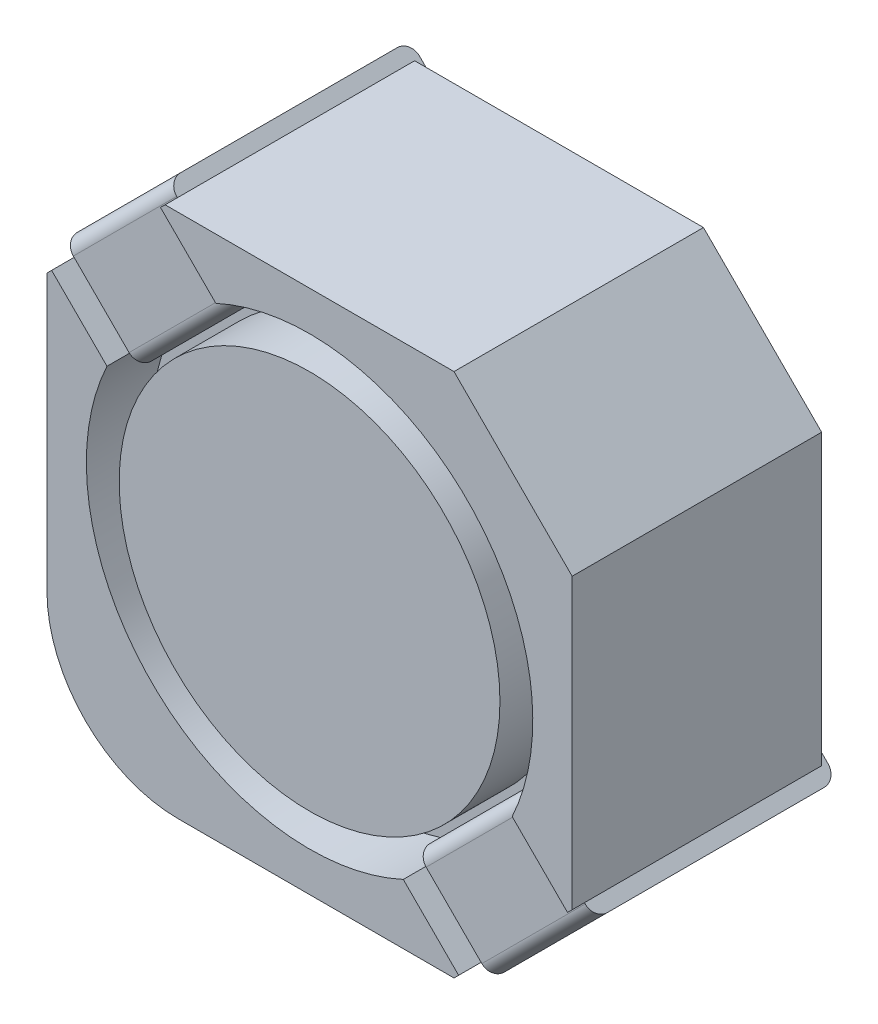
SolidWorks part; units mm, degrees
ref_plane "Спереди" through (0, 0, 0) normal (0, 0, 1) x (1, 0, 0)
ref_plane "Сверху" through (0, 0, 0) normal (0, 1, 0) x (1, 0, 0)
ref_plane "Справа" through (0, 0, 0) normal (1, 0, 0) x (0, 0, -1)
sketch "Эскиз2" plane through (0, 0, 0) normal (0, 0, 1) x (1, 0, 0)
  line L1 (-1.1, 2) -> (1.1, 2)
  line L2 (-2, 1.1) -> (-2, -1)
  line L3 (-1, -2) -> (1.1, -2)
  line L4 (2, 1.1) -> (2, -1.1)
  line L6 (-2, 1.1) -> (-1.1, 2)
  line L8 (1.1, 2) -> (2, 1.1)
  line L9 (1.1, -2) -> (2, -1.1)
  arc A0 (-2, -1) -> (-1, -2) centre (-1, -1) ccw
  point P0 (-2, 2)
  point P1 (2, -2)
  point P3 (2, 2)
  dimension "D1" = 1
extrude "Вытянуть1" add sketch "Эскиз2" along normal blind 1.9 from offset 0.1
sketch "Эскиз6" plane through (0, 0, 0) normal (0, 0, 1) x (1, 0, 0)
  circle A1 centre (0, 0) radius 1.7
extrude "Вытянуть5" cut sketch "Эскиз6" along normal blind 0.3
sketch "Эскиз8" plane through (0, 0, 0) normal (0, 0, 1) x (1, 0, 0)
  circle A0 centre (0, 0) radius 1.45
extrude "Вытянуть9" add sketch "Эскиз8" along normal blind 0.25 from offset 0.1
ref_plane "Плоскость1" through (-0.45, -0.45, 0) normal (0.7071, 0.7071, 0) x (0, 0, -1)
sketch "Эскиз10" plane through (-0.45, -0.45, 0) normal (0.7071, 0.7071, 0) x (0, 0, -1)
  line L0 (0, 1.6) -> (0, 2.2)
  line L1 (-0.1, 2.3) -> (-1.75, 2.3)
  line L2 (-1.85, 2.2) -> (-1.85, 1.6)
  line L3 (0, 0) -> (-3.3921, 0) construction
  line L4 (-1.75, -1.5) -> (-0.1, -1.5)
  line L5 (-1.75, 1.5) -> (-0.1, 1.5)
  line L6 (-1.85, -2.2) -> (-1.85, -1.6)
  line L7 (-0.1, -2.3) -> (-1.75, -2.3)
  line L8 (0, -1.6) -> (0, -2.2)
  arc A0 (0, 2.2) -> (-0.1, 2.3) centre (-0.1, 2.2) ccw
  arc A1 (0, 1.6) -> (-0.1, 1.5) centre (-0.1, 1.6) cw
  arc A2 (-1.85, 1.6) -> (-1.75, 1.5) centre (-1.75, 1.6) ccw
  arc A3 (-1.75, 2.3) -> (-1.85, 2.2) centre (-1.75, 2.2) ccw
  arc A4 (-1.75, -2.3) -> (-1.85, -2.2) centre (-1.75, -2.2) cw
  arc A5 (-1.85, -1.6) -> (-1.75, -1.5) centre (-1.75, -1.6) cw
  arc A6 (0, -1.6) -> (-0.1, -1.5) centre (-0.1, -1.6) ccw
  arc A7 (0, -2.2) -> (-0.1, -2.3) centre (-0.1, -2.2) cw
ref_plane "Плоскость2" through (0.45, 0.45, 0) normal (-0.7071, -0.7071, 0) x (0.7071, -0.7071, 0)
extrude "Вытянуть12" cut sketch "Эскиз6<3>" against normal blind 0.6 from offset 2.1
sketch "Эскиз6<3>" plane through (0, 0, 0) normal (0, 0, 1) x (1, 0, 0) same geometry as "Эскиз6"
sketch "Эскиз12" plane through (-0.45, -0.45, 0) normal (0.7071, 0.7071, 0) x (0, 0, -1)
  line L0 (-3.9996, 0) -> (-2.5383, 0) construction
  line L1 (-3.05, 2.3) -> (-1.7, 2.3)
  line L2 (-3.05, 2.3) -> (-3.05, 1.5)
  line L3 (-3.05, 1.5) -> (-1.7, 1.5)
  line L4 (-1.7, 2.3) -> (-1.7, 1.5)
  line L5 (0, 0) -> (-3.3921, 0) construction
  line L6 (-1.7, -2.3) -> (-1.7, -1.5)
  line L7 (-3.05, -1.5) -> (-1.7, -1.5)
  line L8 (-3.05, -2.3) -> (-3.05, -1.5)
  line L9 (-3.05, -2.3) -> (-1.7, -2.3)
extrude "Вытянуть15" cut sketch "Эскиз12" along normal offset from surface (1.1728 mm away) 0.05 from offset 0.05 up to plane "Плоскость2"
extrude "Вытянуть16" add sketch "Эскиз8<3>" against normal blind 0.7 from offset 2
sketch "Эскиз8<3>" plane through (0, 0, 0) normal (0, 0, 1) x (1, 0, 0) same geometry as "Эскиз8"
extrude "Вытянуть17" add sketch "Эскиз10" along normal offset from surface (1.1128 mm away) 0.08 from offset 0.08 up to plane "Плоскость2"
